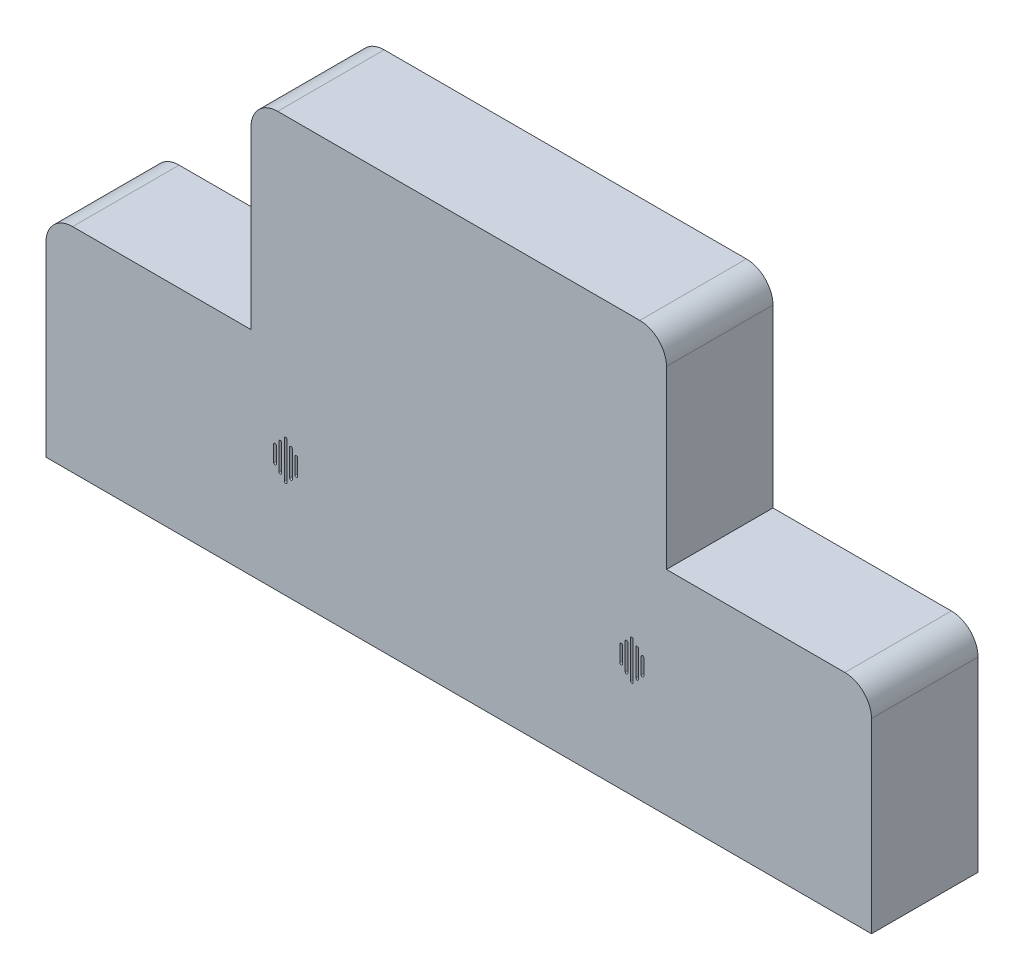
SolidWorks part; units mm, degrees
ref_plane "Front Plane" through (0, 0, 0) normal (0, 0, 1) x (1, 0, 0)
ref_plane "Top Plane" through (0, 0, 0) normal (0, 1, 0) x (1, 0, 0)
ref_plane "Right Plane" through (0, 0, 0) normal (1, 0, 0) x (0, 0, -1)
sketch "Sketch1" plane through (0, 0, 0) normal (0, 1, 0) x (1, 0, 0)
  line L1 (-77.5, 10) -> (77.5, 10)
  line L2 (-77.5, 10) -> (-77.5, -10)
  line L3 (-77.5, -10) -> (77.5, -10)
  line L4 (77.5, 10) -> (77.5, -10)
  line L5 (-77.5, 10) -> (77.5, -10) construction
  line L6 (-77.5, -10) -> (77.5, 10) construction
  point P0 (0, 0)
  dimension "D1" = 155
  dimension "D2" = 20
extrude "Boss-Extrude1" add sketch "Sketch1" along normal blind 40
sketch "Sketch2" plane through (0, 0, 0) normal (0, -1, 0) x (1, 0, 0)
  line L1 (-71, -8) -> (71, -8)
  line L2 (-76, -3) -> (-76, 3)
  line L3 (-71, 8) -> (71, 8)
  line L4 (76, -3) -> (76, 3)
  line L5 (-76, -8) -> (76, 8) construction
  line L6 (-76, 8) -> (76, -8) construction
  arc A0 (71, 8) -> (76, 3) centre (71, 3) cw
  arc A1 (71, -8) -> (76, -3) centre (71, -3) ccw
  arc A2 (-71, -8) -> (-76, -3) centre (-71, -3) cw
  arc A3 (-76, 3) -> (-71, 8) centre (-71, 3) cw
  point P0 (0, 0)
  dimension "D3" = 5
  dimension "D1" = 152
  dimension "D2" = 16
extrude "Cut-Extrude1" cut sketch "Sketch2" against normal blind 3
sketch "Sketch3" plane through (0, 3, 0) normal (0, -1, 0) x (1, 0, 0)
  line L6 (76, 0) -> (-49924, 0) construction
  line L7 (76, -3) -> (76, 3) construction
  line L8 (66.6937, 0) -> (62.1937, 5.5) construction
  line L9 (62.1937, -5.5) -> (71.1937, -5.5) construction
  line L10 (62.1937, -5.5) -> (62.1937, 5.5) construction
  line L11 (62.1937, 5.5) -> (71.1937, 5.5) construction
  line L12 (71.1937, -5.5) -> (71.1937, 5.5) construction
  line L13 (62.1937, -5.5) -> (66.6937, 0) construction
  line L14 (66.6937, 0) -> (71.1937, -5.5) construction
  line L15 (66.6937, 0) -> (71.1937, 5.5) construction
  circle A0 centre (64.4437, 2.75) radius 1.6
  circle A1 centre (68.9437, 2.75) radius 1.6
  circle A2 centre (68.9437, -2.75) radius 1.6
  circle A3 centre (64.4437, -2.75) radius 1.6
  point P4 (76, 0)
  point P5 (66.6937, 0)
  dimension "D3" = 3.2
  dimension "D1" = 9
  dimension "D2" = 11
sketch "Sketch4" plane through (0, 0, 10) normal (0, 0, 1) x (1, 0, 0)
  line L0 (0, 40) -> (0, 50040) construction
  line L1 (-77.5, 40) -> (77.5, 40) construction
  line L8 (39, 78) -> (-39, 78)
  line L9 (39, 78) -> (39, 40)
  line L10 (39, 40) -> (-39, 40)
  line L11 (-39, 78) -> (-39, 40)
  line L12 (39, 78) -> (-39, 40) construction
  line L13 (39, 40) -> (-39, 78) construction
  point P4 (0, 40)
  point P5 (0, 59)
  line M7 (77.5, 40) -> (-77.5, 40)
  dimension "D1" = 39
  dimension "D2" = 38
extrude "Boss-Extrude2" add sketch "Sketch4" against normal up to surface (20 mm away) contours L10 M7 region at (0, 59, 10) up to face at (0, 20, -10)
fillet "Fillet1" radius 5 4 edges at (39, 78, 0) (-39, 78, 0) (77.5, 40, 0) (-77.5, 40, 0)
shell "Shell2" thickness 2 removed face at (0, 44.6785, -10)
sketch "Sketch6" plane through (0, 0, 8) normal (0, 0, -1) x (-1, 0, 0)
  line L1 (-36.476, 69.2849) -> (0.524, 69.2849)
  line L2 (-36.476, 69.2849) -> (-36.476, 29.2849)
  line L3 (-36.476, 29.2849) -> (0.524, 29.2849)
  line L4 (0.524, 69.2849) -> (0.524, 29.2849)
  line L5 (-36.476, 69.2849) -> (0.524, 29.2849) construction
  line L6 (-36.476, 29.2849) -> (0.524, 69.2849) construction
  line L7 (0.5066, 29.2849) -> (37.5066, 29.2849)
  line L8 (0.5066, 29.2849) -> (0.5066, 69.2849)
  line L9 (0.5066, 69.2849) -> (37.5066, 69.2849)
  line L10 (37.5066, 29.2849) -> (37.5066, 69.2849)
  line L11 (0.5066, 29.2849) -> (37.5066, 69.2849) construction
  line L12 (0.5066, 69.2849) -> (37.5066, 29.2849) construction
  point P0 (-17.976, 49.2849)
  point P5 (0, 0)
  point P6 (18.9539, 50.4566)
  point P7 (0, 0)
  point P8 (-17.976, 49.2849)
  point P9 (0, 0)
  point P10 (0, 0)
  point P11 (0, 0)
  point P12 (0, 0)
  point P13 (19.0066, 49.2849)
  point P18 (19.0066, 49.2849)
  dimension "D1" = 40
  dimension "D2" = 37
  dimension "D3" = 37
  dimension "D4" = 40
sketch "Sketch7" plane through (0, 0, 10) normal (0, 0, 1) x (1, 0, 0)
  line L0 (0, 76) -> (0, 3) construction
  line L1 (34, 76) -> (-34, 76) construction
  line L2 (71, 3) -> (-71, 3) construction
  line L3 (-32.5, 22) -> (32.5, 22) construction
  line L4 (75.5, 5) -> (-75.5, 5) construction
  line L5 (-32.5, 18.5) -> (-32.5, 25.5) construction
  line L6 (-32.75, 18.5) -> (-32.75, 25.5)
  line L7 (-32.25, 18.5) -> (-32.25, 25.5)
  line L8 (-31.5, 19.5) -> (-31.5, 24.5) construction
  line L9 (-31.75, 19.5) -> (-31.75, 24.5)
  line L10 (-31.25, 19.5) -> (-31.25, 24.5)
  line L11 (-30.5, 20.5) -> (-30.5, 23.5) construction
  line L12 (-30.75, 20.5) -> (-30.75, 23.5)
  line L13 (-30.25, 20.5) -> (-30.25, 23.5)
  line L14 (-32.5, 22) -> (-32.5, 50022) construction
  line L15 (-33.5, 19.5) -> (-33.5, 24.5) construction
  line L16 (-33.25, 19.5) -> (-33.25, 24.5)
  line L17 (-33.75, 19.5) -> (-33.75, 24.5)
  line L18 (-34.5, 20.5) -> (-34.5, 23.5) construction
  line L19 (-34.25, 20.5) -> (-34.25, 23.5)
  line L20 (-34.75, 20.5) -> (-34.75, 23.5)
  arc A0 (-32.75, 18.5) -> (-32.25, 18.5) centre (-32.5, 18.5) ccw
  arc A1 (-32.25, 25.5) -> (-32.75, 25.5) centre (-32.5, 25.5) ccw
  arc A2 (-31.75, 19.5) -> (-31.25, 19.5) centre (-31.5, 19.5) ccw
  arc A3 (-31.25, 24.5) -> (-31.75, 24.5) centre (-31.5, 24.5) ccw
  arc A4 (-30.75, 20.5) -> (-30.25, 20.5) centre (-30.5, 20.5) ccw
  arc A5 (-30.25, 23.5) -> (-30.75, 23.5) centre (-30.5, 23.5) ccw
  arc A6 (-33.25, 19.5) -> (-33.75, 19.5) centre (-33.5, 19.5) cw
  arc A7 (-33.75, 24.5) -> (-33.25, 24.5) centre (-33.5, 24.5) cw
  arc A8 (-34.25, 20.5) -> (-34.75, 20.5) centre (-34.5, 20.5) cw
  arc A9 (-34.75, 23.5) -> (-34.25, 23.5) centre (-34.5, 23.5) cw
  point P9 (0, 22)
  point P13 (-32.5, 22)
  point P20 (-31.5, 22)
  point P27 (-30.5, 22)
  point P36 (-33.5, 22)
  point P43 (-34.5, 22)
  dimension "D1" = 65
  dimension "D2" = 17
  dimension "D3" = 0.5
  dimension "D4" = 0.5
  dimension "D5" = 0.5
  dimension "D6" = 1
  dimension "D7" = 1
  dimension "D8" = 7
  dimension "D9" = 5
  dimension "D10" = 3
extrude "Cut-Extrude3" cut sketch "Sketch7" against normal through all
mirror "Mirror1" about plane through (0, 0, 0) normal (1, 0, 0) of "Cut-Extrude3"
sketch "Sketch8" plane through (0, 3, 0) normal (0, -1, 0) x (1, 0, 0)
  circle A0 centre (0, 0) radius 8
extrude "Cut-Extrude4" cut sketch "Sketch8" against normal up to next
sketch "Sketch9" plane through (0, 3, 0) normal (0, -1, 0) x (1, 0, 0)
  line L0 (76, 0) -> (-49924, 0) construction
  line L1 (76, -3) -> (76, 3) construction
  line L2 (68.5, 0) -> (64, 5.5) construction
  line L3 (64, -5.5) -> (73, -5.5) construction
  line L4 (64, -5.5) -> (64, 5.5) construction
  line L5 (64, 5.5) -> (73, 5.5) construction
  line L6 (73, -5.5) -> (73, 5.5) construction
  line L7 (64, -5.5) -> (68.5, 0) construction
  line L8 (68.5, 0) -> (73, -5.5) construction
  line L9 (68.5, 0) -> (73, 5.5) construction
  line L10 (68.5, 5.5) -> (68.5, -5.5) construction
  circle A0 centre (70.75, 2.75) radius 2.05
  circle A1 centre (66.25, 2.75) radius 2.05
  circle A2 centre (66.25, -2.75) radius 2.05
  circle A3 centre (70.75, -2.75) radius 2.05
  point P4 (76, 0)
  point P5 (68.5, 0)
  point P19 (0, 0)
  dimension "D4" = 4.1
  dimension "D1" = 9
  dimension "D2" = 11
  dimension "D3" = 3
extrude "Cut-Extrude5" cut sketch "Sketch9" against normal blind 1.1
mirror "Mirror2" about plane through (0, 0, 0) normal (1, 0, 0) of "Cut-Extrude5"
sketch "Sketch10" plane through (0, 0, 10) normal (0, 0, 1) x (1, 0, 0)
  line L1 (-33.9831, 34.5762) -> (-1.9831, 34.5762)
  line L2 (-33.9831, 34.5762) -> (-33.9831, 75.0762)
  line L3 (-33.9831, 75.0762) -> (-1.9831, 75.0762)
  line L4 (-1.9831, 34.5762) -> (-1.9831, 75.0762)
  line L5 (2.0173, 75.0762) -> (34.0173, 75.0762)
  line L6 (2.0173, 75.0762) -> (2.0173, 34.5762)
  line L7 (2.0173, 34.5762) -> (34.0173, 34.5762)
  line L8 (34.0173, 75.0762) -> (34.0173, 34.5762)
  point P4 (34.0173, 34.5762)
  point P5 (0, 0)
  point P6 (-1.9831, 34.5762)
  dimension "D1" = 32
  dimension "D2" = 40.5
  dimension "D3" = 32
  dimension "D4" = 40.5
